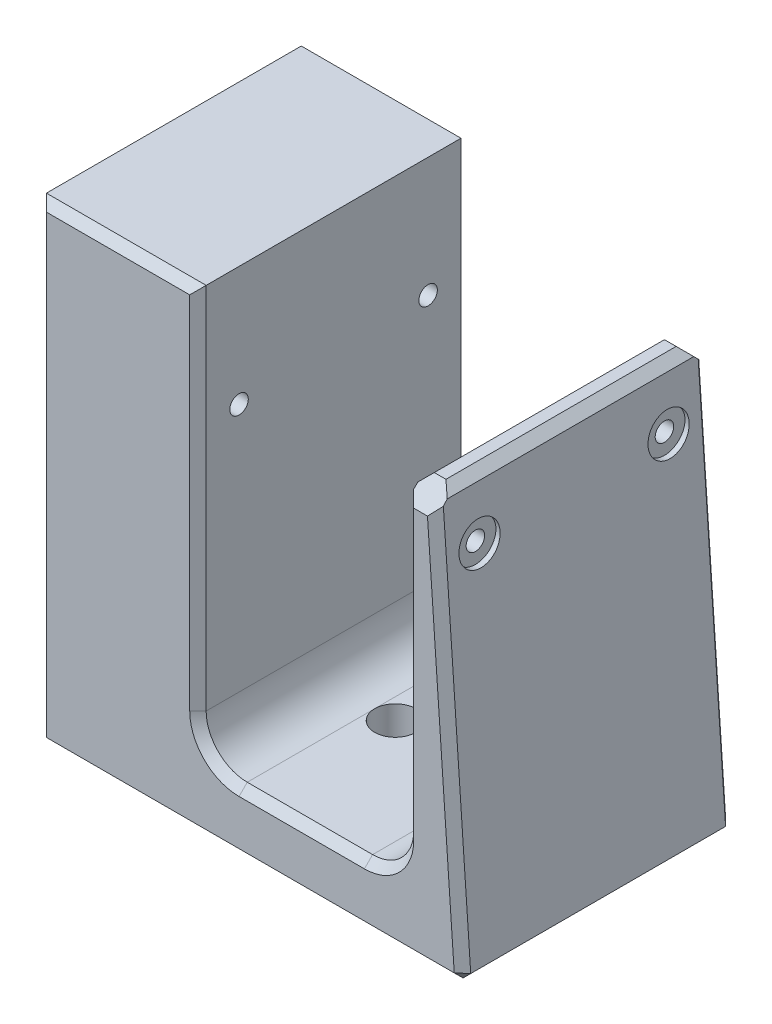
SolidWorks part; units mm, degrees
material "ABS"
ref_plane "Piano frontale" through (0, 0, 0) normal (0, 0, 1) x (1, 0, 0)
ref_plane "Piano superiore" through (0, 0, 0) normal (0, 1, 0) x (1, 0, 0)
ref_plane "Piano destro" through (0, 0, 0) normal (1, 0, 0) x (0, 0, -1)
sketch "Schizzo1" plane through (0, 0, 0) normal (0, 0, 1) x (1, 0, 0)
  line L0 (25.25, 100) -> (32.25, 100)
  line L1 (32.25, 100) -> (39.25, 0)
  line L2 (39.25, 0) -> (-39.25, 0)
  line L3 (-39.25, 0) -> (-32.25, 100) construction
  line L4 (-32.25, 100) -> (-25.25, 100) construction
  line L5 (-25.25, 100) -> (-25.25, 15)
  line L6 (-25.25, 15) -> (25.25, 15)
  line L7 (25.25, 15) -> (25.25, 100)
  line L8 (0, 15) -> (0, 0) construction
  line L9 (-25.25, 100) -> (-25.25, 114.69)
  line L10 (-25.25, 114.69) -> (-64.1103, 114.69)
  line L11 (-64.1103, 114.69) -> (-64.1103, 0)
  line L12 (-64.1103, 0) -> (-39.25, 0)
  point P2 (0, 0)
  dimension "D1" = 7
  dimension "D2" = 50.5
  dimension "D3" = 14
  dimension "D4" = 100
  dimension "D5" = 85
  dimension "D6" = 38.8603
  dimension "D7" = 14.69
extrude "Estrusione-Estrusione1" add sketch "Schizzo1" along normal blind 66
fillet "Raccordo1" radius 10 2 edges at (-25.25, 15, 33) (25.25, 15, 33)
chamfer "Smusso1" distance 2 angle 45 21 edges at (32.25, 100, 33) (39.25, 0, 33) (25.25, 62.5, 66) (22.3211, 17.9289, 66) (0, 15, 66) (-22.3211, 17.9289, 66) (-25.25, 69.845, 66) (35.75, 50, 66) (-12.4302, 0, 66) (25.25, 62.5, 0) (22.3211, 17.9289, 0) (0, 15, 0) (-22.3211, 17.9289, 0) (-25.25, 69.845, 0) (-12.4302, 0, 0) (35.75, 50, 0) (25.25, 100, 33) (-64.1103, 57.345, 66) (-64.1103, 57.345, 0) (-44.6802, 114.69, 66) (-44.6802, 114.69, 0)
chamfer "Smusso2" distance 5 angle 45 2 edges at (28.6721, 100, 66) (28.6721, 100, 0)
ref_plane "Piano1" through (-35.25, 0, 0) normal (1, 0, 0) x (0, 0, -1)
ref_plane "Piano2" through (35.25, 0, 0) normal (-1, 0, 0) x (0, 0, 1)
sketch "Schizzo4" plane through (35.25, 0, 0) normal (-1, 0, 0) x (0, 0, 1)
  line L1 (56, 85.6136) -> (10, 85.6136) construction
  line L3 (2, 0) -> (64, 0) construction
  line L4 (66, 2) -> (66, 95) construction
  point P0 (56, 85.6136)
  point P2 (10, 85.6136)
  dimension "D1" = 85.6136
  dimension "D2" = 10
  dimension "D3" = 46
hole_wizard "Foro lamato per Vite M4 a testa cilindrica piana-2" positions "Schizzo4" profile "Schizzo5" counterbore size "M4" standard "ISO"
sketch "Schizzo5" plane through (35.25, 85.6136, 56) normal (0, 1, 0) x (0, 0, -1)
  line L0 (0, 0) -> (0, 31.3519)
  line L1 (0, 31.3519) -> (2.25, 30)
  line L2 (2.25, 30) -> (2.25, 3)
  line L3 (2.25, 3) -> (5, 3)
  line L4 (5, 3) -> (5, 0)
  line L5 (5, 0) -> (0, 0)
  line L10 (0, 31.3519) -> (-2.25, 30) construction
  line L11 (0, -6.35) -> (0, 107.95) construction
  dimension "Hole Dia." = 4.5
  dimension "Hole Depth" = 30
  dimension "C'Bore Dia." = 10
  dimension "C'Bore Depth" = 3
  dimension "Drill Angle" = 118
hole_wizard "Foro lamato per Vite M4 a testa cilindrica piana-3" positions "Schizzo6" profile "Schizzo7" counterbore size "M4" standard "ISO"
sketch "Schizzo6" plane through (0, 15, 0) normal (0, 1, 0) x (1, 0, 0)
  line L0 (-10.2456, -33) -> (9.7544, -33) construction
  line L2 (25.25, -2) -> (25.25, -64) construction
  line L3 (-15.25, 0) -> (15.25, 0) construction
  point P0 (-10.2456, -33)
  point P2 (9.7544, -33)
  dimension "D1" = 20
  dimension "D2" = 15.4956
  dimension "D3" = 33
sketch "Schizzo7" plane through (-10.2456, 15, 33) normal (1, 0, 0) x (0, 0, 1)
  line L0 (0, 0) -> (0, 31.3519)
  line L1 (0, 31.3519) -> (2.25, 30)
  line L2 (2.25, 30) -> (2.25, 10)
  line L3 (2.25, 10) -> (5, 10)
  line L4 (5, 10) -> (5, 0)
  line L5 (5, 0) -> (0, 0)
  line L10 (0, 31.3519) -> (-2.25, 30) construction
  line L11 (0, -6.35) -> (0, 107.95) construction
  dimension "Hole Dia." = 4.5
  dimension "Hole Depth" = 30
  dimension "C'Bore Dia." = 10
  dimension "C'Bore Depth" = 10
  dimension "Drill Angle" = 118
sketch "Schizzo8" plane through (-64.1103, 0, 0) normal (-1, 0, 0) x (0, 0, 1)
  line L0 (10, 85.6136) -> (56, 85.6136) construction
  line L2 (66, 112.69) -> (66, 2) construction
  line L3 (64, 0) -> (2, 0) construction
  point P0 (10, 85.6136)
  point P2 (56, 85.6136)
  dimension "D1" = 46
  dimension "D2" = 10
  dimension "D3" = 85.6136
hole_wizard "Foro lamato per Vite M4 a testa cilindrica piana-4" positions "Schizzo8" profile "Schizzo9" counterbore size "M4" standard "ISO"
sketch "Schizzo9" plane through (-64.1103, 85.6136, 10) normal (0, 1, 0) x (0, 0, 1)
  line L0 (0, 0) -> (0, 46.3519)
  line L1 (0, 46.3519) -> (2.25, 45)
  line L2 (2.25, 45) -> (2.25, 32)
  line L3 (2.25, 32) -> (5, 32)
  line L4 (5, 32) -> (5, 0)
  line L5 (5, 0) -> (0, 0)
  line L10 (0, 46.3519) -> (-2.25, 45) construction
  line L11 (0, -6.35) -> (0, 107.95) construction
  dimension "Hole Dia." = 4.5
  dimension "Hole Depth" = 45
  dimension "C'Bore Dia." = 10
  dimension "C'Bore Depth" = 32
  dimension "Drill Angle" = 118
